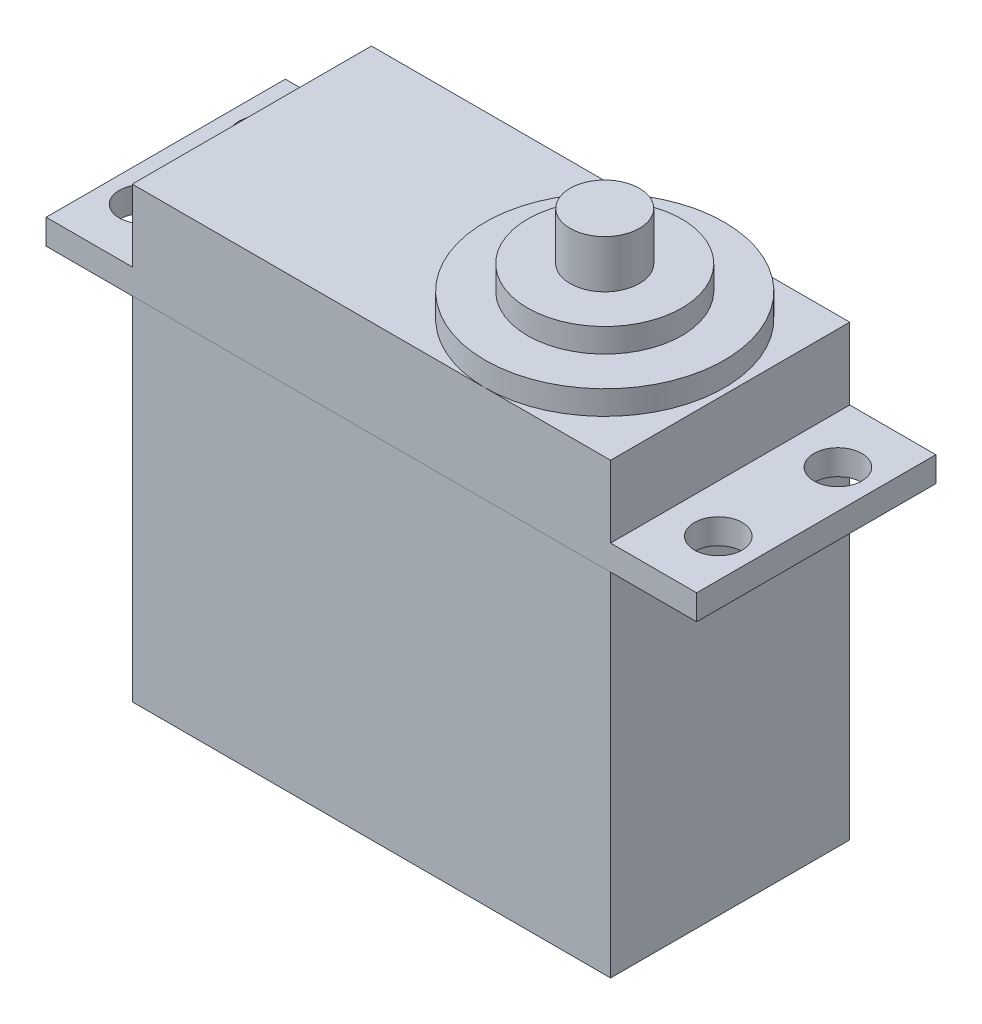
SolidWorks part; units mm, degrees
ref_plane "Alzado" through (0, 0, 0) normal (0, 0, 1) x (1, 0, 0)
ref_plane "Planta" through (0, 0, 0) normal (0, 1, 0) x (1, 0, 0)
ref_plane "Vista lateral" through (0, 0, 0) normal (1, 0, 0) x (0, 0, -1)
sketch "Croquis1" plane through (0, 0, 0) normal (0, 1, 0) x (1, 0, 0)
  line L0 (0, 0) -> (40, 0)
  line L1 (40, 0) -> (40, -20)
  line L2 (0, 0) -> (0, -20)
  line L3 (0, -20) -> (40, -20)
extrude "Saliente-Extruir1" add sketch "Croquis1" along normal blind 29.4
sketch "Croquis2" plane through (0, 29.4, 0) normal (0, 1, 0) x (1, 0, 0)
  line L0 (20, 0) -> (-7.2, 0)
  line L1 (40, 0) -> (0, 0) construction
  line L2 (20, 0) -> (47.2, 0)
  line L3 (-7.2, 0) -> (-7.2, -20.0033)
  line L4 (-7.2, -20.0033) -> (47.2, -20.0033)
  line L5 (47.2, -20.0033) -> (47.2, 0)
extrude "Saliente-Extruir2" add sketch "Croquis2" along normal blind 2.1
sketch "Croquis3" plane through (0, 31.5, 0) normal (0, 1, 0) x (1, 0, 0)
  circle A0 centre (-4.0958, -5.0008) radius 2
  circle A1 centre (-4.0958, -15.0025) radius 2
  circle A2 centre (44.0105, -5.0008) radius 2
  circle A3 centre (44.0105, -15.0025) radius 2
extrude "Cortar-Extruir1" cut sketch "Croquis3" against normal blind 2.1
sketch "Croquis4" plane through (0, 31.5, 0) normal (0, 1, 0) x (1, 0, 0)
  line L2 (0, 0) -> (0, -20.0033)
  line L3 (-7.2, -20.0033) -> (47.2, -20.0033) construction
  line L4 (0, -20.0033) -> (40.0016, -20.0033)
  line L5 (40.0016, -20.0033) -> (40, 0)
  line L6 (40, 0) -> (0, 0)
extrude "Saliente-Extruir3" add sketch "Croquis4" along normal blind 6
sketch "Croquis5" plane through (0, 37.5, 0) normal (0, 1, 0) x (1, 0, 0)
  line L0 (40.0008, -10.0017) -> (29.5104, -10.0017)
  line L1 (40.0016, -20.0033) -> (40, 0) construction
  circle A0 centre (29.5104, -10.0017) radius 10.0017
extrude "Saliente-Extruir4" add sketch "Croquis5" along normal blind 2 contours A0 region at (19.7916, 37.5, 10.0017)
sketch "Croquis6" plane through (0, 39.5, 0) normal (0, 1, 0) x (1, 0, 0)
  circle A0 centre (29.5104, -10.0017) radius 6.45
extrude "Saliente-Extruir5" add sketch "Croquis6" along normal blind 2
sketch "Croquis7" plane through (0, 41.5, 0) normal (0, 1, 0) x (1, 0, 0)
  circle A0 centre (29.5104, -10.0017) radius 2.9
extrude "Saliente-Extruir6" add sketch "Croquis7" along normal blind 4
